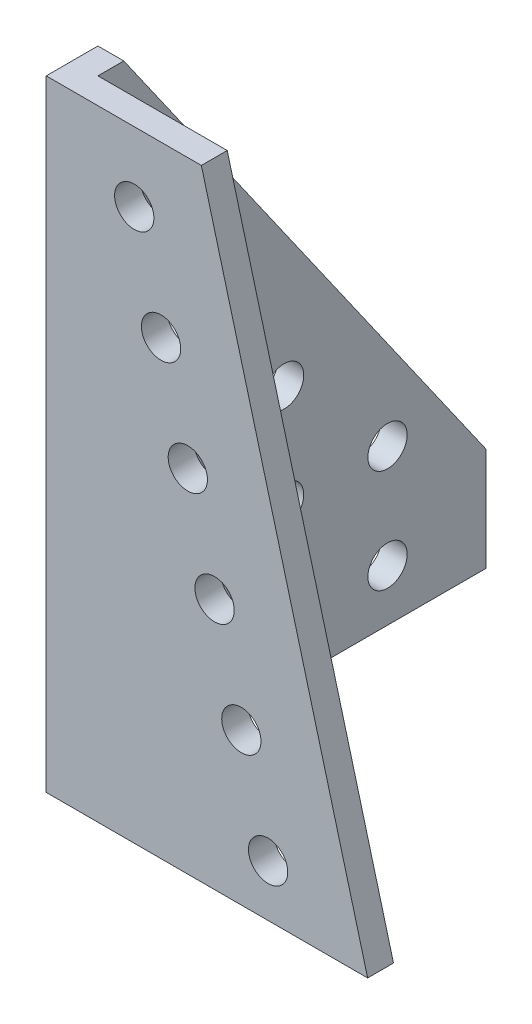
SolidWorks part; units mm, degrees
ref_plane "Front Plane" through (0, 0, 0) normal (0, 0, 1) x (1, 0, 0)
ref_plane "Top Plane" through (0, 0, 0) normal (0, 1, 0) x (1, 0, 0)
ref_plane "Right Plane" through (0, 0, 0) normal (1, 0, 0) x (0, 0, -1)
sketch "Sketch1" plane through (0, 0, 0) normal (0, 1, 0) x (1, 0, 0)
  line L0 (0, 0) -> (0, 50.8)
  line L1 (0, 50.8) -> (3.175, 50.8)
  line L2 (3.175, 50.8) -> (3.175, 3.175)
  line L3 (3.175, 3.175) -> (50.8, 3.175)
  line L4 (50.8, 3.175) -> (50.8, 0)
  line L5 (50.8, 0) -> (0, 0)
  dimension "D1" = 50.8
  dimension "D2" = 50.8
  dimension "D3" = 3.175
  dimension "D4" = 3.175
extrude "Boss-Extrude1" add sketch "Sketch1" along normal blind 76.2
sketch "Sketch2" plane through (0, 0, -3.175) normal (0, 0, -1) x (-1, 0, 0)
  line L2 (-17.3868, 43.1518) -> (-27.2478, 6.35) construction
  line L3 (-50.8, 0) -> (-3.175, 0) construction
  line L5 (-19.05, 76.2) -> (-50.8, -42.2926)
  line L6 (-50.8, 76.2) -> (-3.175, 76.2) construction
  line L7 (-50.8, 76.2) -> (-50.8, 0) construction
  line L8 (-50.8, -42.2926) -> (-50.8, 76.2)
  line L9 (-50.8, 76.2) -> (-19.05, 76.2)
  circle A0 centre (-27.2478, 6.35) radius 2.413
  circle A1 centre (-23.9608, 18.6173) radius 2.413
  circle A2 centre (-20.6738, 30.8845) radius 2.413
  circle A3 centre (-17.3868, 43.1518) radius 2.413
  circle A4 centre (-14.0998, 55.419) radius 2.413
  circle A5 centre (-10.8128, 67.6863) radius 2.413
  dimension "D1" = 12.7
  dimension "D2" = 4.826
  dimension "D3" = 12.7
  dimension "D4" = 12.7
  dimension "D6" = 10.16
  dimension "D8" = 6.35
  dimension "D5" = 75
  dimension "D7" = 3
  dimension "D9" = 31.75
sketch "Sketch3" plane through (3.175, 0, 0) normal (1, 0, 0) x (0, 0, -1)
  line L0 (13.335, 6.35) -> (13.335, 46.2046) construction
  line L1 (26.035, 6.35) -> (26.035, 46.2046) construction
  line L2 (3.175, 0) -> (50.8, 0) construction
  line L3 (3.175, 43.1518) -> (3.175, 6.35) construction
  line L4 (6.35, 76.2) -> (50.8, 12.7188)
  line L6 (50.8, 76.2) -> (50.8, 0) construction
  line L7 (50.8, 12.7188) -> (50.8, 76.2)
  line L8 (50.8, 76.2) -> (6.35, 76.2)
  circle A0 centre (13.335, 6.35) radius 2.413
  circle A1 centre (26.035, 6.35) radius 2.413
  circle A2 centre (13.335, 19.05) radius 2.413
  circle A3 centre (26.035, 19.05) radius 2.413
  circle A4 centre (13.335, 31.75) radius 2.413
  circle A5 centre (26.035, 31.75) radius 2.413
  circle A6 centre (13.335, 44.45) radius 2.413
  circle A7 centre (38.735, 19.05) radius 2.413
  circle A8 centre (38.735, 6.35) radius 2.413
  point P18 (3.175, 24.7509)
  dimension "D1" = 4.826
  dimension "D2" = 4.826
  dimension "D4" = 6.35
  dimension "D5" = 6.35
  dimension "D8" = 4.826
  dimension "D9" = 12.7
  dimension "D6" = 10.16
  dimension "D7" = 22.86
  dimension "D11" = 55
  dimension "D12" = 44.45
  dimension "D3" = 3
  dimension "D10" = 2
extrude "Cut-Extrude1" cut sketch "Sketch2" against normal through all
extrude "Cut-Extrude2" cut sketch "Sketch3" against normal through all
